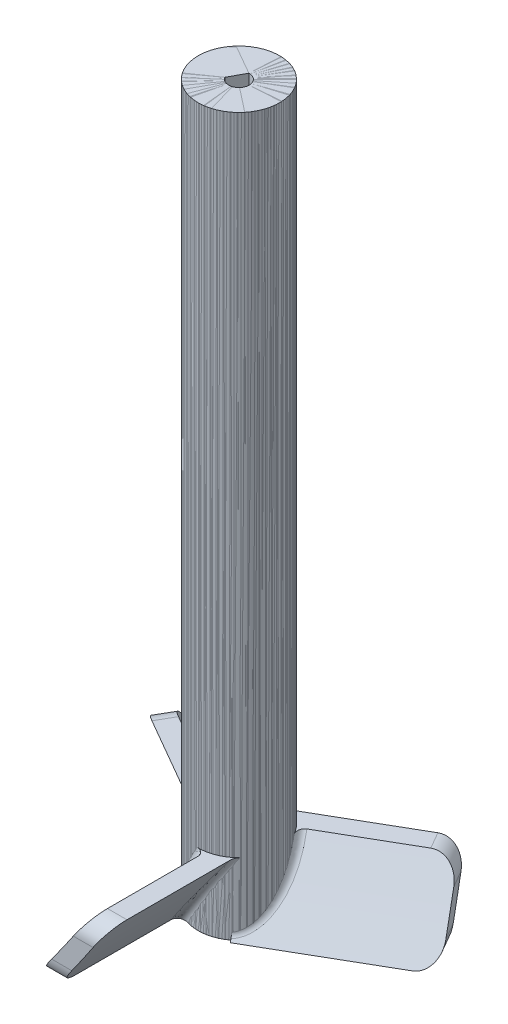
SolidWorks part; units mm, degrees
ref_plane "Front Plane" through (0, 0, 0) normal (0, 0, 1) x (1, 0, 0)
ref_plane "Top Plane" through (0, 0, 0) normal (0, 1, 0) x (1, 0, 0)
ref_plane "Right Plane" through (0, 0, 0) normal (1, 0, 0) x (0, 0, -1)
sketch "Sketch7" plane through (0, 0, 0) normal (0, 0, 1) x (1, 0, 0)
  line L0 (14.5391, 0) -> (-14.5391, 0) construction
  line L1 (6.849, 7) -> (4.9497, 7)
  line L2 (0, 0) -> (2, 0)
  arc A0 (0, 0) -> (4.9497, 7) centre (-91.3778, 69.8639) ccw
  arc A1 (6.849, 7) -> (2, 0) centre (-91.3778, 69.8639) cw
  dimension "D2" = 7
extrude "Boss-Extrude2" add sketch "Sketch7" along normal blind 15 contours A0 L1 A1 L2
fillet "Fillet1" radius 2 2 edges at (1, 0, 15) (5.8994, 7, 15)
sketch "Sketch10" plane through (0, 0, 0) normal (0, 1, 0) x (1, 0, 0)
  line L0 (0.3156, 0) -> (8.1957, 0) construction
  line L1 (4.9497, 0) -> (0, 0) construction
  line L2 (6.849, 0) -> (4.9497, 0) construction
  line L3 (2, 0) -> (6.849, 0) construction
  line L4 (4.2556, 0) -> (4.2556, 0.5251)
  line L5 (3.1481, -1000) -> (3.1481, 49000) construction
  circle A0 centre (4.2556, 0.5251) radius 3.9749
  point P5 (3.1481, 0)
  point P10 (-1.8519, 0)
  point P17 (3.1481, 0)
  dimension "D4" = 5
extrude "Boss-Extrude3" add sketch "Sketch10" along normal blind 70 contours A0 region at (0.3932, 0, -0.5251)
fillet "Fillet4" radius 0.7 2 edges at (1.2681, 1.6905, 2.0967) (3.7358, 2.3821, 3.4156)
pattern_circular "CirPattern1" count 3 over 360 about axis through (4.2556, 70, -0.5251) along (0, -1, 0) of bodies 103 102
sketch "Sketch11" plane through (0, 70, 0) normal (0, 1, 0) x (1, 0, 0)
  line L0 (3.4046, 0) -> (4.2264, 1.5247)
  arc A1 (3.4046, 0) -> (4.2264, 1.5247) centre (4.2556, 0.5251) ccw
  circle A2 centre (4.2556, 0.5251) radius 3.9749 construction
extrude "Cut-Extrude1" cut sketch "Sketch11" against normal blind 40 contours A1 L0
equation "\"insidebladediameter\"=0.01"
equation "\"height\"= 0.007"
equation "\"bladethickness\"=0.002"
equation "\"insidebladeradius\"= \"insidebladediameter\" / 2"
equation "\"D1@Sketch7\"=\"bladethickness\""
equation "\"D2@Sketch7\"=\"height\""
equation "\"bladewidth\"= \"height\" * cos ( \"bladeangle\" )"
equation "\"bladelength\"= 0.015"
equation "\"D1@Boss-Extrude2\"=\"bladelength\""
equation "\"bladetipradius\"= 0.002"
equation "\"D1@Fillet1\"=\"bladetipradius\""
equation "\"fusedistance\"= 0.0045"
equation "\"motorrodheight\"=0.07"
equation "\"D1@Boss-Extrude3\"=\"motorrodheight\""
equation "\"numberofblades\"= 3"
equation "\"D1@CirPattern1\"=\"numberofblades\""
equation "\"roddiameter\"= ( \"bladewidth\" + 0.003 )"
equation "\"roddepth\"= 0.005"
equation "\"bladeangle\"= 45deg"
equation "\"m\"=1"
equation "\"flatfacedist\"= 0.0005"
equation "\"motorshaftdiameter\"=0.002"
equation "\"D1@Sketch11\"=\"motorshaftdiameter\"/2"
equation "\"D3@Sketch7\"=\"bladewidth\""
equation "\"D2@Sketch10\"=\"roddiameter\"/2-\"fusedistance\""
equation "\"D1@Sketch10\"=\"roddiameter\""
equation "\"D2@Sketch11\"=\"flatfacedist\""
equation "\"bladefilletradius\"= 0.0007"
equation "\"D1@Fillet4\"=\"bladefilletradius\""
